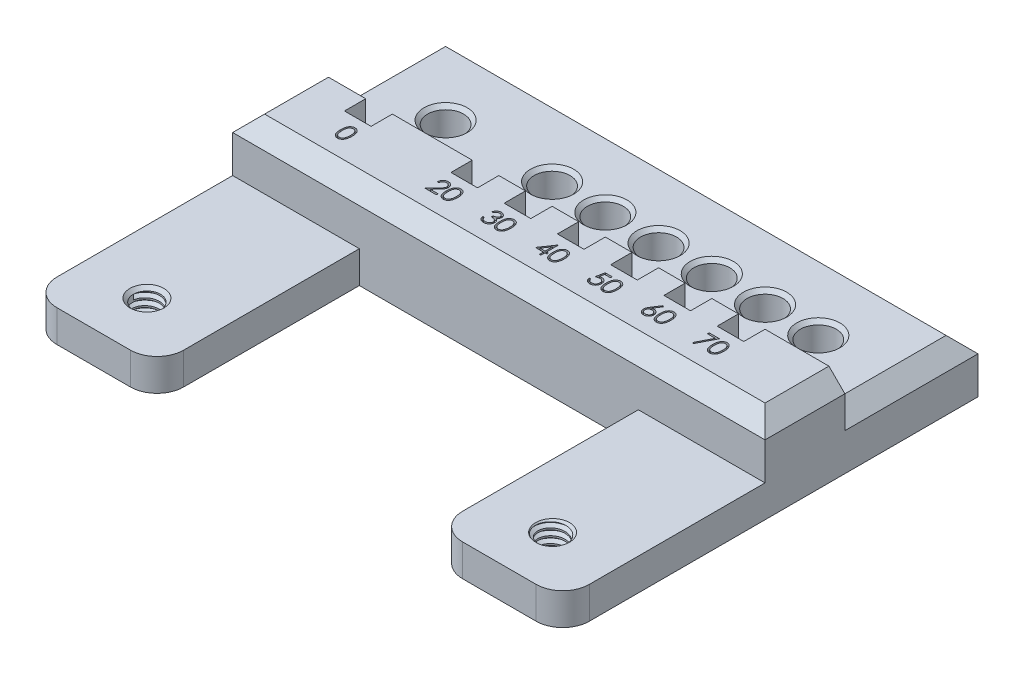
SolidWorks part; units mm, degrees
ref_plane "Front Plane" through (0, 0, 0) normal (0, 0, 1) x (1, 0, 0)
ref_plane "Top Plane" through (0, 0, 0) normal (0, 1, 0) x (1, 0, 0)
ref_plane "Right Plane" through (0, 0, 0) normal (1, 0, 0) x (0, 0, -1)
sketch "Sketch2" plane through (0, 0, 0) normal (1, 0, 0) x (0, 0, -1)
  line L0 (0, 0) -> (40, 0)
  line L1 (40, 0) -> (40, 10)
  line L2 (40, 10) -> (15, 10)
  line L3 (15, 10) -> (15, 16)
  line L4 (15, 16) -> (0, 16)
  line L5 (0, 16) -> (0, 0)
  dimension "D1" = 10
  dimension "D2" = 6
  dimension "D3" = 15
  dimension "D4" = 25
extrude "Boss-Extrude1" add sketch "Sketch2" along normal blind 100
sketch "Sketch3" plane through (0, 10, 0) normal (0, 1, 0) x (1, 0, 0)
  line L0 (0, 25) -> (100, 25) construction
  line L1 (0, 40) -> (0, 15) construction
  line L2 (100, 40) -> (100, 15) construction
  line L3 (100, 15) -> (0, 15) construction
  line L4 (15, 25) -> (15, 15) construction
  line L5 (25, 25) -> (25, 15) construction
  line L6 (35, 25) -> (35, 15) construction
  line L7 (45, 25) -> (45, 15) construction
  line L8 (55, 25) -> (55, 15) construction
  line L9 (65, 25) -> (65, 15) construction
  line L10 (75, 25) -> (75, 15) construction
  line L11 (85, 25) -> (85, 15) construction
  dimension "D1" = 10
  dimension "D2" = 15
  dimension "D3" = 8
hole_wizard "1/4 Clearance Hole1" positions "Sketch4" profile "Sketch5" hole size "1/4" standard "ANSI Inch" end condition through all
sketch "Sketch4" plane through (0, 10, 0) normal (0, 1, 0) x (1, 0, 0)
  point P0 (15, 25)
  point P3 (35, 25)
  point P6 (45, 25)
  point P9 (55, 25)
  point P12 (65, 25)
  point P16 (75, 25)
  point P19 (85, 25)
sketch "Sketch5" plane through (15, 10, -25) normal (1, 0, 0) x (0, 0, 1)
  line L0 (0, 0) -> (0, 10)
  line L1 (0, 10) -> (4.064, 10)
  line L2 (3.3782, 9.3142) -> (3.3782, 0.6858)
  line L3 (3.3782, 0.6858) -> (4.064, 0)
  line L5 (4.064, 0) -> (0, 0)
  line L6 (-3.3782, 0.6858) -> (-4.064, 0) construction
  line L7 (4.064, 10) -> (3.3782, 9.3142)
  line L8 (-4.064, 10) -> (-3.3782, 9.3142) construction
  line L11 (0, -6.35) -> (0, 107.95) construction
  dimension "Thru Hole Dia." = 6.7564
  dimension "Thru Hole Depth" = 10
  dimension "Near C'Sink Dia." = 8.128
  dimension "Near C'Sink Angle" = 90
  dimension "Far C'Sink Dia." = 8.128
  dimension "Far C'Sink Angle" = 90
sketch "Sketch6" plane through (0, 16, 0) normal (0, 1, 0) x (1, 0, 0)
  line L0 (100, 15) -> (0, 15) construction
  line L1 (15, 15) -> (10, 15)
  line L2 (15, 15) -> (15, 11)
  line L3 (15, 11) -> (10, 11)
  line L4 (10, 15) -> (10, 11)
  line L5 (15, 25) -> (15, 15) construction
  line L6 (25, 11) -> (20, 11) [skipped]
  line L7 (25, 15) -> (25, 11) [skipped]
  line L8 (25, 15) -> (20, 15) [skipped]
  line L9 (20, 15) -> (20, 11) [skipped]
  line L10 (35, 11) -> (30, 11)
  line L11 (35, 15) -> (35, 11)
  line L12 (35, 15) -> (30, 15)
  line L13 (30, 15) -> (30, 11)
  line L14 (45, 11) -> (40, 11)
  line L15 (45, 15) -> (45, 11)
  line L16 (45, 15) -> (40, 15)
  line L17 (40, 15) -> (40, 11)
  line L18 (55, 11) -> (50, 11)
  line L19 (55, 15) -> (55, 11)
  line L20 (55, 15) -> (50, 15)
  line L21 (50, 15) -> (50, 11)
  line L22 (65, 11) -> (60, 11)
  line L23 (65, 15) -> (65, 11)
  line L24 (65, 15) -> (60, 15)
  line L25 (60, 15) -> (60, 11)
  line L26 (75, 11) -> (70, 11)
  line L27 (75, 15) -> (75, 11)
  line L28 (75, 15) -> (70, 15)
  line L29 (70, 15) -> (70, 11)
  line L30 (85, 11) -> (80, 11)
  line L31 (85, 15) -> (85, 11)
  line L32 (85, 15) -> (80, 15)
  line L33 (80, 15) -> (80, 11)
  dimension "D1" = 5
  dimension "D2" = 4
extrude "Cut-Extrude1" cut sketch "Sketch6" against normal up to surface (6 mm away) and the other way through all up to face at (15, 10, -20.936)
sketch "Sketch7" plane through (0, 16, 0) normal (0, 1, 0) x (1, 0, 0)
  line L0 (10, 11) -> (15, 11) construction
  line L1 (20, 6) -> (25, 6) construction
  line L2 (30, 6) -> (35, 6) construction
  line L3 (40, 6) -> (45, 6) construction
  line L4 (10, 6) -> (15, 6) construction
  line L5 (10, 11) -> (10, 6) construction
  line L6 (15, 11) -> (15, 6) construction
  line L7 (50, 6) -> (55, 6) construction
  line L8 (60, 6) -> (65, 6) construction
  line L9 (70, 6) -> (75, 6) construction
  line L10 (80, 6) -> (85, 6) construction
  line L11 (90, 6) -> (95, 6) construction
  text T0 "20"
  text T1 "0"
  text T2 "30"
  text T3 "40"
  text T4 "50"
  text T5 "60"
  text T6 "70"
  dimension "D1" = 5
  dimension "D2" = 9
extrude "Cut-Extrude2" cut sketch "Sketch7" against normal blind 0.6
chamfer "Chamfer1" distance 3 angle 45 6 edges at (0, 16, -7.5) (100, 16, -7.5) (50, 16, 0) (100, 10, -27.5) (50, 10, -40) (0, 10, -27.5)
sketch "Sketch8" plane through (0, 0, 0) normal (0, -1, 0) x (1, 0, 0)
  line L0 (50, 0) -> (50, -40) construction
  line L1 (100, 0) -> (0, 0) construction
  line L2 (100, -40) -> (0, -40) construction
  line L3 (76.2, 0) -> (76.2, 38)
  line L4 (0, 0) -> (23.8, 0)
  line L5 (0, 0) -> (0, 38)
  line L6 (0, 38) -> (23.8, 38)
  line L7 (23.8, 0) -> (23.8, 38)
  line L8 (100, 38) -> (76.2, 38)
  line L9 (100, 0) -> (100, 38)
  line L10 (100, 0) -> (76.2, 0)
  line L11 (0, 0) -> (0, -40) construction
  point P10 (11.9, 38)
  dimension "D1" = 38
  dimension "D2" = 38.1
extrude "Boss-Extrude2" add sketch "Sketch8" against normal blind 6
hole_wizard "Tap Drill for 1/4-20 Tap1" positions "Sketch9" profile "Sketch10" hole size "1/4-20" standard "ANSI Inch" end condition through all
sketch "Sketch9" plane through (0, 6, 0) normal (0, 1, 0) x (1, 0, 0)
  line L12 (11.9, -28) -> (11.9, -38) construction
  line L13 (23.8, -38) -> (0, -38) construction
  line L15 (88.1, -28) -> (88.1, -38) construction
  line L16 (100, -38) -> (76.2, -38) construction
  line L18 (11.9, -28) -> (88.1, -28) construction
  line L20 (23.8, -38) -> (0, -38) construction
  point P0 (88.1, -28)
  point P2 (11.9, -28)
  dimension "D1" = 10
sketch "Sketch10" plane through (88.1, 6, 28) normal (1, 0, 0) x (0, 0, 1)
  line L0 (0, 0) -> (0, 6)
  line L1 (0, 6) -> (3.1877, 6)
  line L2 (2.5527, 5.365) -> (2.5527, 0.635)
  line L3 (2.5527, 0.635) -> (3.1877, 0)
  line L5 (3.1877, 0) -> (0, 0)
  line L6 (-2.5527, 0.635) -> (-3.1877, 0) construction
  line L7 (3.1877, 6) -> (2.5527, 5.365)
  line L8 (-3.1877, 6) -> (-2.5527, 5.365) construction
  line L11 (0, -6.35) -> (0, 107.95) construction
  dimension "Thru Hole Dia." = 5.1054
  dimension "Thru Hole Depth" = 6
  dimension "Near C'Sink Dia." = 6.3754
  dimension "Near C'Sink Angle" = 90
  dimension "Far C'Sink Dia." = 6.3754
  dimension "Far C'Sink Angle" = 90
thread "Thread1" pitch 1.27 method cut trim with start face yes trim with end face yes profile "Thread Profile1" start angle 0, offset 0, length 10, pitch 1.27, diameter 5.1054
ref_plane "Plane1" through (90.6527, 0.635, 28) normal (0, 0, 1) x (1, 0, 0)
sketch "Thread Profile1" plane through (90.6527, 0.635, 28) normal (0, 0, 1) x (1, 0, 0)
  line L0 (0, 0) -> (0, 1.27) construction
  line L1 (0, 0) -> (0.6874, 0.3969)
  line L2 (0.6874, 0.3969) -> (0.6874, 0.5556)
  line L3 (0.6874, 0.5556) -> (0, 0.9525)
  line L4 (0.6874, 0.4762) -> (0, 0.4762) construction
  line L11 (0, 0) -> (0, 0.9525)
  point P2 (0, 0)
  dimension "Pitch" = 1.27
  dimension "Profile_Angle" = 60
  dimension "Profile_Land" = 0.1588
  dimension "Profile_Height" = 0.6874
thread "Thread2" pitch 1.27 method cut trim with start face yes trim with end face yes profile "Thread Profile2" start angle 0, offset 0, length 0, pitch 1.27, diameter 5.1054
ref_plane "Plane2" through (9.3473, 5.365, 28) normal (0, 0, 1) x (-1, 0, 0)
sketch "Thread Profile2" plane through (9.3473, 5.365, 28) normal (0, 0, 1) x (-1, 0, 0)
  line L0 (0, 0) -> (0, 1.27) construction
  line L1 (0, 0) -> (0.6874, 0.3969)
  line L2 (0.6874, 0.3969) -> (0.6874, 0.5556)
  line L3 (0.6874, 0.5556) -> (0, 0.9525)
  line L4 (0.6874, 0.4762) -> (0, 0.4762) construction
  line L11 (0, 0) -> (0, 0.9525)
  point P2 (0, 0)
  dimension "Pitch" = 1.27
  dimension "Profile_Angle" = 60
  dimension "Profile_Land" = 0.1588
  dimension "Profile_Height" = 0.6874
fillet "Fillet1" radius 5 4 edges at (0, 3, 38) (23.8, 3, 38) (76.2, 3, 38) (100, 3, 38)
